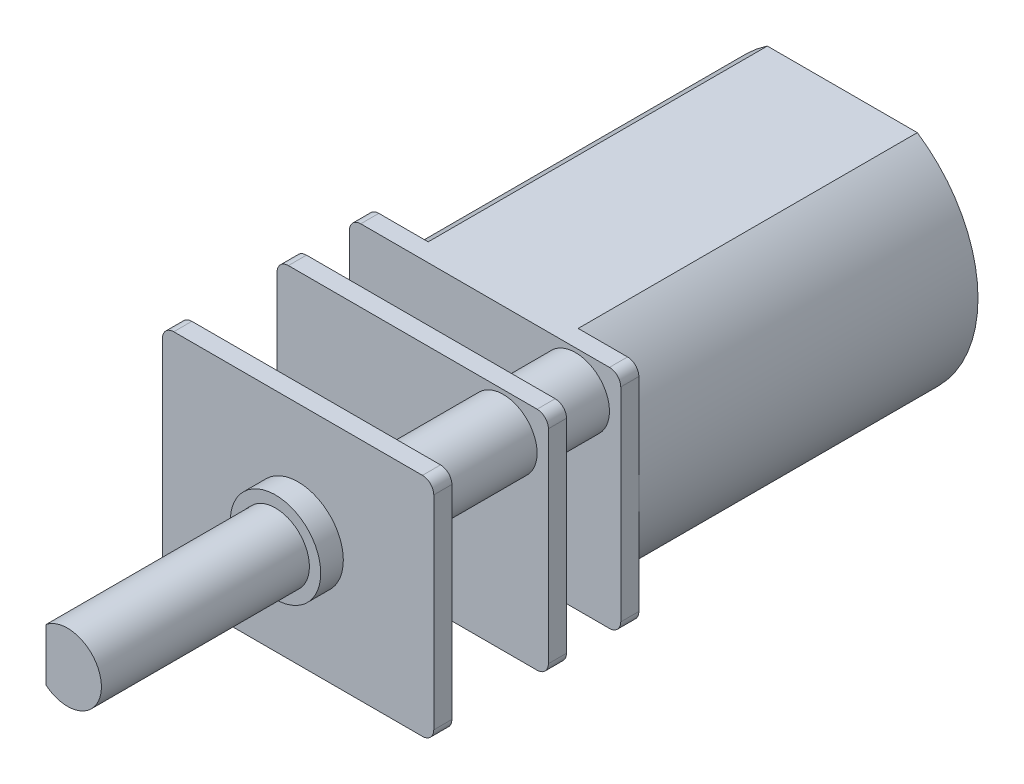
SolidWorks part; units mm, degrees
ref_plane "Alzado" through (0, 0, 0) normal (0, 0, 1) x (1, 0, 0)
ref_plane "Planta" through (0, 0, 0) normal (0, 1, 0) x (1, 0, 0)
ref_plane "Vista lateral" through (0, 0, 0) normal (1, 0, 0) x (0, 0, -1)
sketch "Croquis1" plane through (0, 0, 0) normal (0, 0, 1) x (1, 0, 0)
  line L0 (-3.3166, 5) -> (3.3166, 5)
  line L1 (3.3166, -5) -> (-3.3166, -5)
  line L3 (-3.8, -0.75) -> (-3.5, -0.75)
  line L4 (-3.8, -0.75) -> (-3.8, 0.75)
  line L5 (-3.8, 0.75) -> (-3.5, 0.75)
  line L6 (-3.5, -0.75) -> (-3.5, 0.75)
  line L7 (-3.8, -0.75) -> (-3.5, 0.75) construction
  line L8 (-3.8, 0.75) -> (-3.5, -0.75) construction
  circle A0 centre (0, 0) radius 6
  circle A1 centre (0, 0) radius 2.5
  point P8 (-3.65, 0)
  dimension "D1" = 12
  dimension "D3" = 5
  dimension "D2" = 10
  dimension "D4" = 0.3
  dimension "D5" = 1.5
  dimension "D6" = 3.5
extrude "Saliente-Extruir1" add sketch "Croquis1" along normal blind 15 contours L0 A0 L1 | A1 | L3 L6 L5 L4 region at (0, 4.8438, 0) region at (0, 0, 0)
sketch "Croquis2" plane through (0, 0, 15) normal (0, 0, 1) x (1, 0, 0)
  line L0 (-3.3166, 5) -> (3.3166, 5) construction
  line L1 (-5.5, -5) -> (5.5, -5)
  line L2 (-6, -4.5) -> (-6, 4.5)
  line L3 (-5.5, 5) -> (5.5, 5)
  line L4 (6, -4.5) -> (6, 4.5)
  line L5 (-6, -5) -> (6, 5) construction
  line L6 (-6, 5) -> (6, -5) construction
  arc A0 (3.3166, -5) -> (3.3166, 5) centre (0, 0) ccw construction
  arc A1 (-5.5, -5) -> (-6, -4.5) centre (-5.5, -4.5) cw
  arc A2 (5.5, -5) -> (6, -4.5) centre (5.5, -4.5) ccw
  arc A3 (5.5, 5) -> (6, 4.5) centre (5.5, 4.5) cw
  arc A4 (-6, 4.5) -> (-5.5, 5) centre (-5.5, 4.5) cw
  point P0 (0, 0)
  dimension "D1" = 0.5
extrude "Saliente-Extruir2" add sketch "Croquis2" along normal blind 0.8
sketch "Croquis3" plane through (0, 0, 15.8) normal (0, 0, 1) x (1, 0, 0)
  line L0 (-5.8536, -4.8536) -> (5.8536, 4.8536) construction
  line L1 (6, -4.5) -> (6, 4.5) construction
  circle A0 centre (-3.8536, -3.1952) radius 1.5
  circle A1 centre (4, 3.3167) radius 1.5
  arc A2 (-6, -4.5) -> (-5.5, -5) centre (-5.5, -4.5) ccw construction
  arc A3 (6, 4.5) -> (5.5, 5) centre (5.5, 4.5) ccw construction
  dimension "D1" = 3
  dimension "D2" = 2
  dimension "D3" = 2
extrude "Saliente-Extruir3" add sketch "Croquis3" along normal blind 2.4
sketch "Croquis4" plane through (0, 0, 18.2) normal (0, 0, 1) x (1, 0, 0)
  line L0 (5.5, 5) -> (-5.5, 5) construction
  line L1 (-6, 4.5) -> (-6, -4.5) construction
  line L2 (-5.5, -5) -> (5.5, -5) construction
  line L3 (6, -4.5) -> (6, 4.5) construction
  line L4 (5.5, 5) -> (-5.5, 5)
  line L5 (-6, 4.5) -> (-6, -4.5)
  line L6 (-5.5, -5) -> (5.5, -5)
  line L7 (6, -4.5) -> (6, 4.5)
  arc A3 (-5.5, 5) -> (-6, 4.5) centre (-5.5, 4.5) ccw construction
  arc A4 (-6, -4.5) -> (-5.5, -5) centre (-5.5, -4.5) ccw construction
  arc A5 (5.5, -5) -> (6, -4.5) centre (5.5, -4.5) ccw construction
  arc A6 (6, 4.5) -> (5.5, 5) centre (5.5, 4.5) ccw construction
  arc A7 (-5.5, 5) -> (-6, 4.5) centre (-5.5, 4.5) ccw
  arc A8 (-6, -4.5) -> (-5.5, -5) centre (-5.5, -4.5) ccw
  arc A9 (5.5, -5) -> (6, -4.5) centre (5.5, -4.5) ccw
  arc A10 (6, 4.5) -> (5.5, 5) centre (5.5, 4.5) ccw
extrude "Saliente-Extruir4" add sketch "Croquis4" along normal blind 0.8
sketch "Croquis5" plane through (0, 0, 19) normal (0, 0, 1) x (1, 0, 0)
  circle A1 centre (4, 3.3167) radius 1.5
  circle A2 centre (4, 3.3167) radius 1.5
  circle A3 centre (-3.8536, -3.1952) radius 1.5
  circle A4 centre (-3.8536, -3.1952) radius 1.5
  dimension "D1" = 0
  dimension "D2" = 0
extrude "Saliente-Extruir5" add sketch "Croquis5" along normal blind 4.27
sketch "Croquis6" plane through (0, 0, 23.27) normal (0, 0, 1) x (1, 0, 0)
  line L4 (5.5, 5) -> (-5.5, 5)
  line L5 (-6, 4.5) -> (-6, -4.5)
  line L6 (-5.5, -5) -> (5.5, -5)
  line L7 (6, -4.5) -> (6, 4.5)
  line L8 (5.5, 5) -> (-5.5, 5)
  line L9 (-6, 4.5) -> (-6, -4.5)
  line L10 (-5.5, -5) -> (5.5, -5)
  line L11 (6, -4.5) -> (6, 4.5)
  arc A4 (6, 4.5) -> (5.5, 5) centre (5.5, 4.5) ccw
  arc A5 (-5.5, 5) -> (-6, 4.5) centre (-5.5, 4.5) ccw
  arc A6 (-6, -4.5) -> (-5.5, -5) centre (-5.5, -4.5) ccw
  arc A7 (5.5, -5) -> (6, -4.5) centre (5.5, -4.5) ccw
  arc A8 (6, 4.5) -> (5.5, 5) centre (5.5, 4.5) ccw
  arc A9 (-5.5, 5) -> (-6, 4.5) centre (-5.5, 4.5) ccw
  arc A10 (-6, -4.5) -> (-5.5, -5) centre (-5.5, -4.5) ccw
  arc A11 (5.5, -5) -> (6, -4.5) centre (5.5, -4.5) ccw
  dimension "D1" = 0
extrude "Saliente-Extruir6" add sketch "Croquis6" along normal blind 0.8
sketch "Croquis7" plane through (0, 0, 24.07) normal (0, 0, 1) x (1, 0, 0)
  circle A0 centre (0, 0) radius 2
  dimension "D1" = 4
extrude "Saliente-Extruir7" add sketch "Croquis7" along normal blind 1
sketch "Croquis8" plane through (0, 0, 25.07) normal (0, 0, 1) x (1, 0, 0)
  circle A0 centre (0, 0) radius 1.5
  dimension "D1" = 3
extrude "Saliente-Extruir8" add sketch "Croquis8" along normal blind 9.2
sketch "Croquis9" plane through (0, 0, 34.27) normal (0, 0, 1) x (1, 0, 0)
  line L0 (-0.95, 1.1608) -> (-0.95, -1.1608)
  circle A0 centre (0, 0) radius 1.5
  circle A1 centre (0, 0) radius 1.5 construction
  circle M1 centre (0, 0) radius 1.5
  dimension "D1" = 0.95
extrude "Cortar-Extruir1" cut sketch "Croquis9" against normal blind 9 contours L0 M1 region at (-1.1739, 0, 34.27)
extrude "Saliente-Extruir9" add sketch "Croquis1<3>" against normal blind 1 contours A1
sketch "Croquis1<3>" plane through (0, 0, 0) normal (0, 0, 1) x (1, 0, 0) same geometry as "Croquis1"
extrude "Saliente-Extruir10" add sketch "Croquis1<4>" against normal blind 1.3 contours L4 L5 L6 L3
sketch "Croquis1<4>" plane through (0, 0, 0) normal (0, 0, 1) x (1, 0, 0) same geometry as "Croquis1"
sketch "Croquis10" plane through (-3.8, 0, 0) normal (-1, 0, 0) x (0, 0, 1)
  line L0 (-1.3, -0.75) -> (-1.3, 0.75) construction
  line L1 (-1.3, 0.75) -> (0, 0.75) construction
  circle A0 centre (-0.65, 0) radius 0.35
  point P4 (-1.3, 0)
  point P7 (-0.65, 0.75)
  dimension "D1" = 0.7
extrude "Cortar-Extruir2" cut sketch "Croquis10" against normal up to next
mirror "Simetría1" about plane through (0, 0, 0) normal (1, 0, 0) of "Cortar-Extruir2", "Saliente-Extruir10"
